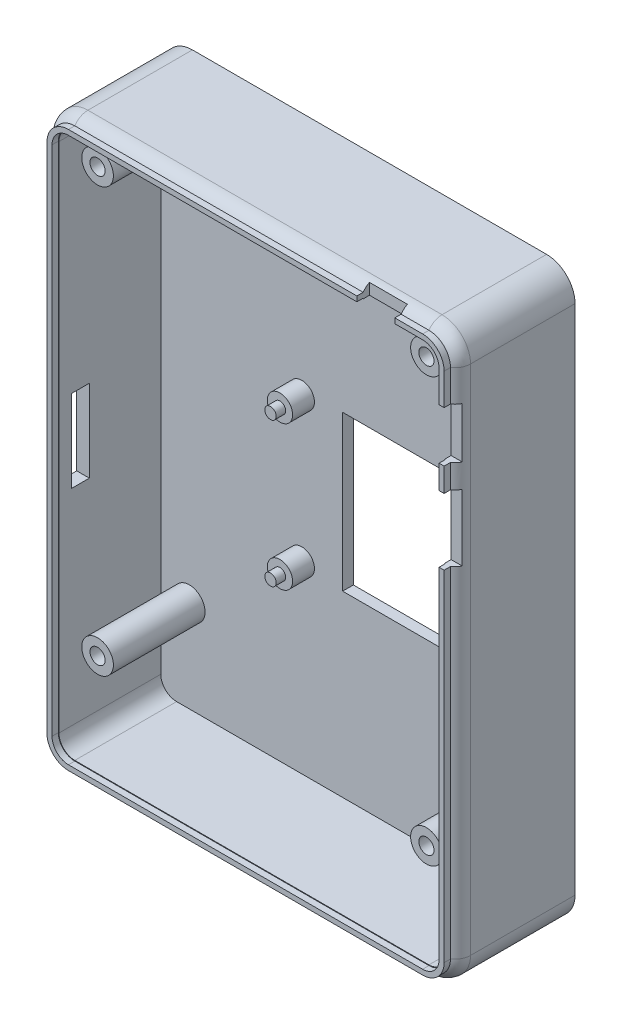
SolidWorks part; units mm, degrees
ref_plane "前基準面" through (0, 0, 0) normal (0, 0, 1) x (1, 0, 0)
ref_plane "上基準面" through (0, 0, 0) normal (0, 1, 0) x (1, 0, 0)
ref_plane "右基準面" through (0, 0, 0) normal (1, 0, 0) x (0, 0, -1)
sketch "草圖1" plane through (0, 0, 0) normal (0, 0, 1) x (1, 0, 0)
  line L0 (2, -87.5) -> (58, -87.5)
  line L1 (62.5, -83) -> (62.5, -2)
  line L2 (58, 2.5) -> (2, 2.5)
  line L3 (-2.5, -2) -> (-2.5, -83)
  arc A0 (58, -87.5) -> (62.5, -83) centre (58, -83) ccw
  arc A1 (62.5, -2) -> (58, 2.5) centre (58, -2) ccw
  arc A2 (2, 2.5) -> (-2.5, -2) centre (2, -2) ccw
  arc A3 (-2.5, -83) -> (2, -87.5) centre (2, -83) ccw
extrude "floor" add sketch "草圖1" along normal blind 2.5
sketch "草圖2" plane through (0, 0, 0) normal (0, 0, 1) x (1, 0, 0)
  line L0 (2, -87.5) -> (58, -87.5)
  line L1 (62.5, -83) -> (62.5, -2)
  line L2 (58, 2.5) -> (2, 2.5)
  line L3 (-2.5, -2) -> (-2.5, -83)
  line L4 (2, -86.5) -> (58, -86.5)
  line L5 (61.5, -83) -> (61.5, -2)
  line L6 (58, 1.5) -> (2, 1.5)
  line L7 (-1.5, -2) -> (-1.5, -83)
  arc A0 (58, -87.5) -> (62.5, -83) centre (58, -83) ccw
  arc A1 (62.5, -2) -> (58, 2.5) centre (58, -2) ccw
  arc A2 (2, 2.5) -> (-2.5, -2) centre (2, -2) ccw
  arc A3 (-2.5, -83) -> (2, -87.5) centre (2, -83) ccw
  arc A4 (58, -86.5) -> (61.5, -83) centre (58, -83) ccw
  arc A5 (61.5, -2) -> (58, 1.5) centre (58, -2) ccw
  arc A6 (2, 1.5) -> (-1.5, -2) centre (2, -2) ccw
  arc A7 (-1.5, -83) -> (2, -86.5) centre (2, -83) ccw
extrude "wall outer half" add sketch "草圖2" along normal blind 18.6
sketch "草圖3" plane through (0, 0, 0) normal (0, 0, 1) x (1, 0, 0)
  line L0 (2, -86.5) -> (58, -86.5)
  line L1 (61.5, -83) -> (61.5, -2)
  line L2 (58, 1.5) -> (2, 1.5)
  line L3 (-1.5, -2) -> (-1.5, -83)
  line L4 (2, -85.5) -> (58, -85.5)
  line L5 (60.5, -83) -> (60.5, -2)
  line L6 (58, 0.5) -> (2, 0.5)
  line L7 (-0.5, -2) -> (-0.5, -83)
  arc A0 (58, -86.5) -> (61.5, -83) centre (58, -83) ccw
  arc A1 (61.5, -2) -> (58, 1.5) centre (58, -2) ccw
  arc A2 (2, 1.5) -> (-1.5, -2) centre (2, -2) ccw
  arc A3 (-1.5, -83) -> (2, -86.5) centre (2, -83) ccw
  arc A4 (58, -85.5) -> (60.5, -83) centre (58, -83) ccw
  arc A5 (60.5, -2) -> (58, 0.5) centre (58, -2) ccw
  arc A6 (2, 0.5) -> (-0.5, -2) centre (2, -2) ccw
  arc A7 (-0.5, -83) -> (2, -85.5) centre (2, -83) ccw
extrude "wall inner half" add sketch "草圖3" along normal blind 18.6
sketch "草圖4" plane through (0, 0, 0) normal (0, 0, 1) x (1, 0, 0)
  line L0 (2, -86.4) -> (58, -86.4)
  line L1 (61.4, -83) -> (61.4, -2)
  line L2 (58, 1.4) -> (2, 1.4)
  line L3 (-1.4, -2) -> (-1.4, -83)
  line L4 (2, -85.6) -> (58, -85.6)
  line L5 (60.6, -83) -> (60.6, -2)
  line L6 (58, 0.6) -> (2, 0.6)
  line L7 (-0.6, -2) -> (-0.6, -83)
  arc A0 (58, -86.4) -> (61.4, -83) centre (58, -83) ccw
  arc A1 (61.4, -2) -> (58, 1.4) centre (58, -2) ccw
  arc A2 (2, 1.4) -> (-1.4, -2) centre (2, -2) ccw
  arc A3 (-1.4, -83) -> (2, -86.4) centre (2, -83) ccw
  arc A4 (58, -85.6) -> (60.6, -83) centre (58, -83) ccw
  arc A5 (60.6, -2) -> (58, 0.6) centre (58, -2) ccw
  arc A6 (2, 0.6) -> (-0.6, -2) centre (2, -2) ccw
  arc A7 (-0.6, -83) -> (2, -85.6) centre (2, -83) ccw
extrude "lip" add sketch "草圖4" along normal blind 19.6
fillet "screen face round-over" radius 2.5 8 edges at (-1.182, -86.182, 18.6) (-2.5, -42.5, 18.6) (-1.182, 1.182, 18.6) (30, 2.5, 18.6) (61.182, 1.182, 18.6) (62.5, -42.5, 18.6) (61.182, -86.182, 18.6) (30, -87.5, 18.6)
sketch "草圖5" plane through (0, 0, 0) normal (0, 0, 1) x (1, 0, 0)
  circle A0 centre (4, -4) radius 2.5
  circle A1 centre (56, -4) radius 2.5
  circle A2 centre (4, -71) radius 2.5
  circle A3 centre (56, -71) radius 2.5
extrude "standoffs" add sketch "草圖5" along normal blind 17
sketch "草圖6" plane through (0, 0, 0) normal (0, 0, 1) x (1, 0, 0)
  circle A0 centre (4, -4) radius 1.2
  circle A1 centre (56, -4) radius 1.2
  circle A2 centre (4, -71) radius 1.2
  circle A3 centre (56, -71) radius 1.2
extrude "screw bores" cut sketch "草圖6" along normal through all
sketch "草圖7" plane through (0, 0, 0) normal (0, 0, 1) x (1, 0, 0)
  circle A0 centre (4, -4) radius 2.1
  circle A1 centre (56, -4) radius 2.1
  circle A2 centre (4, -71) radius 2.1
  circle A3 centre (56, -71) radius 2.1
extrude "screw head recesses" cut sketch "草圖7" along normal blind 1.5
sketch "草圖8" plane through (0, 0, 0) normal (0, 0, 1) x (1, 0, 0)
  circle A0 centre (21.8, -33.6) radius 2
  circle A1 centre (21.8, -56.4) radius 2
  circle A2 centre (56, -33.6) radius 2
  circle A3 centre (56, -56.4) radius 2
extrude "display posts" add sketch "草圖8" along normal blind 5.96
sketch "草圖9" plane through (0, 0, 0) normal (0, 0, 1) x (1, 0, 0)
  circle A0 centre (21.8, -33.6) radius 0.9
  circle A1 centre (21.8, -56.4) radius 0.9
  circle A2 centre (56, -33.6) radius 0.9
  circle A3 centre (56, -56.4) radius 0.9
extrude "display pegs" add sketch "草圖9" along normal blind 7.46
sketch "草圖10" plane through (0, 0, 0) normal (0, 0, 1) x (1, 0, 0)
  line L0 (26.25, -59.25) -> (54.75, -59.25)
  line L1 (54.75, -59.25) -> (54.75, -30.75)
  line L2 (54.75, -30.75) -> (26.25, -30.75)
  line L3 (26.25, -30.75) -> (26.25, -59.25)
extrude "screen frame recess" cut sketch "草圖10" along normal blind 0.8
sketch "草圖11" plane through (0, 0, 0) normal (0, 0, 1) x (1, 0, 0)
  line L0 (28.25, -57.25) -> (52.75, -57.25)
  line L1 (52.75, -57.25) -> (52.75, -32.75)
  line L2 (52.75, -32.75) -> (28.25, -32.75)
  line L3 (28.25, -32.75) -> (28.25, -57.25)
extrude "display window" cut sketch "草圖11" along normal through all
sketch "草圖12" plane through (0, 0, 0) normal (0, 0, 1) x (1, 0, 0)
  circle A0 centre (53, -14) radius 1
extrude "charge LED hole D2" cut sketch "草圖12" along normal through all
sketch "草圖13" plane through (0, 0, 0) normal (1, 0, 0) x (0, 0, -1)
  line L0 (-13.8, -50.5) -> (-16.6, -50.5)
  line L1 (-16.6, -50.5) -> (-16.6, -37.5)
  line L2 (-16.6, -37.5) -> (-13.8, -37.5)
  line L3 (-13.8, -37.5) -> (-13.8, -50.5)
extrude "microSD slot" cut sketch "草圖13" against normal through all
sketch "草圖14" plane through (0, 0, 0) normal (1, 0, 0) x (0, 0, -1)
  line L0 (-17.6, -29.25) -> (-20.1, -29.25)
  line L1 (-20.1, -29.25) -> (-20.1, -18.75)
  line L2 (-20.1, -18.75) -> (-17.6, -18.75)
  line L3 (-17.6, -18.75) -> (-17.6, -29.25)
extrude "USB-C lip notch" cut sketch "草圖14" along normal blind 4.5 from offset 59
sketch "草圖15" plane through (0, 0, 0) normal (1, 0, 0) x (0, 0, -1)
  line L0 (-17.6, -15) -> (-20.1, -15)
  line L1 (-20.1, -15) -> (-20.1, -7)
  line L2 (-20.1, -7) -> (-17.6, -7)
  line L3 (-17.6, -7) -> (-17.6, -15)
extrude "switch lip notch" cut sketch "草圖15" along normal blind 4.5 from offset 59
sketch "草圖16" plane through (0, 0, 0) normal (0, 1, 0) x (1, 0, 0)
  line L0 (47.6, -17.6) -> (53.6, -17.6)
  line L1 (53.6, -17.6) -> (53.6, -20.1)
  line L2 (53.6, -20.1) -> (47.6, -20.1)
  line L3 (47.6, -20.1) -> (47.6, -17.6)
extrude "shutter lip notch" cut sketch "草圖16" along normal through all
